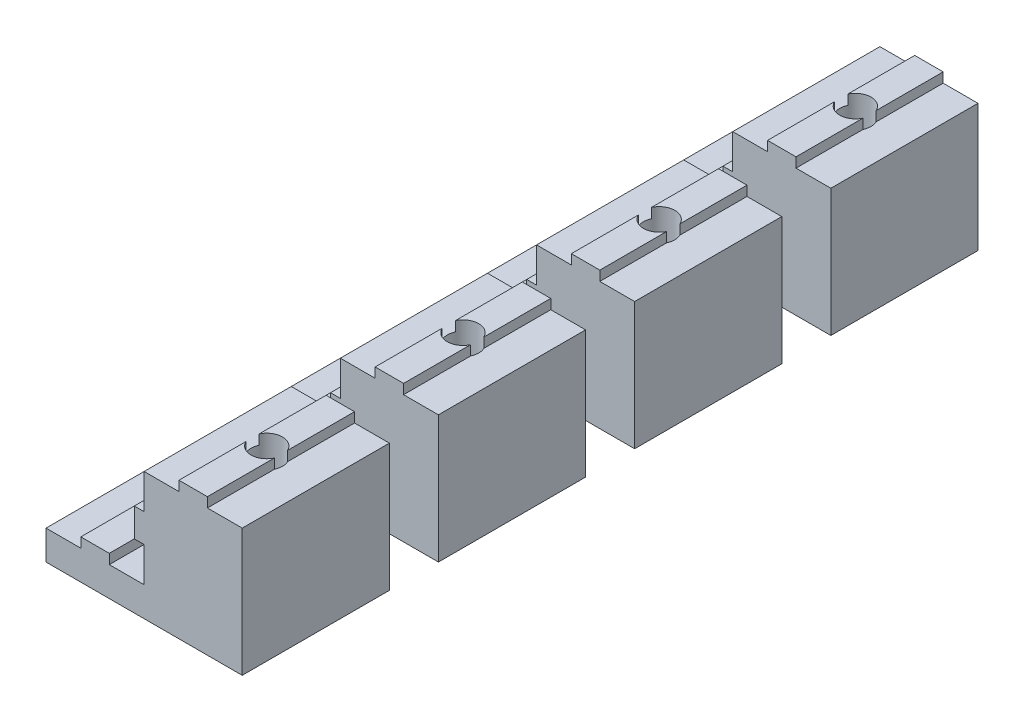
SolidWorks part; units mm, degrees
ref_plane "Front Plane" through (0, 0, 0) normal (0, 0, 1) x (1, 0, 0)
ref_plane "Top Plane" through (0, 0, 0) normal (0, 1, 0) x (1, 0, 0)
ref_plane "Right Plane" through (0, 0, 0) normal (1, 0, 0) x (0, 0, -1)
sketch "Esquisse1" plane through (0, 0, 0) normal (0, 0, 1) x (1, 0, 0)
  line L0 (-20, 0) -> (-20, 3)
  line L1 (-20, 3) -> (-16.45, 3)
  line L2 (-16.45, 3) -> (-16.45, 4)
  line L3 (-16.45, 4) -> (-13.55, 4)
  line L4 (-13.55, 4) -> (-13.55, 3)
  line L5 (-13.55, 3) -> (-10, 3)
  line L6 (-10, 3) -> (-10, 6.55)
  line L7 (0, 0) -> (-20, 0)
  line L8 (-10, 6.55) -> (-11, 6.55)
  line L9 (-11, 6.55) -> (-11, 9.45)
  line L10 (-11, 9.45) -> (-10, 9.45)
  line L11 (-10, 9.45) -> (-10, 13)
  line L12 (-10, 13) -> (-6.45, 13)
  line L13 (0, 13) -> (0, 0)
  line L14 (-6.45, 13) -> (-6.45, 14)
  line L15 (-6.45, 14) -> (-3.55, 14)
  line L16 (-3.55, 14) -> (-3.55, 13)
  line L17 (-3.55, 13) -> (0, 13)
  point P18 (-3.55, 18)
  dimension "D1" = 10
  dimension "D2" = 3
  dimension "D3" = 1
  dimension "D4" = 2.9
  dimension "D5" = 3.55
  dimension "D6" = 10
  dimension "D7" = 2.9
  dimension "D8" = 2.9
  dimension "D9" = 3.55
  dimension "D10" = 1
  dimension "D11" = 13
extrude "Main" add sketch "Esquisse1" along normal blind 15
sketch "Esquisse2" plane through (0, 14, 0) normal (0, 1, 0) x (1, 0, 0)
  line L0 (0, -2.2) -> (0, 2.2) construction
  line L1 (-20, -15) -> (-20, 0) construction
  line L2 (-3.55, 0) -> (-6.45, 0) construction
  line L3 (-13.55, -15) -> (-16.45, -15) construction
  circle A0 centre (-5, -7.5) radius 1.6
  circle A1 centre (-15, -7.5) radius 1.6
  point P11 (0, 0)
  point P12 (0, 0)
  point P14 (-15, -15)
  dimension "D2" = 5
  dimension "D3" = 3.2
  dimension "D1" = 5
  dimension "D4" = 7.5
  dimension "D5" = 7.5
extrude "TopHole" cut sketch "Esquisse2" against normal through all
ref_axis "Axe1" through (-5.5, 0, 0) along (1, 0, 0)
ref_axis "Axe2" through (15.9625, 0, 0) along (-1, 0, 0)
sketch "Sketch1" plane through (0, 0, 0) normal (0, -1, 0) x (-1, 0, 0)
  circle A0 centre (5, -7.5) radius 4.25
  dimension "D1" = 8.5
extrude "Cut-Extrude1" cut sketch "Sketch1" against normal blind 10
pattern_linear "LPattern1" count 4 spacing 20 along (0, 0, 1) of bodies 114
